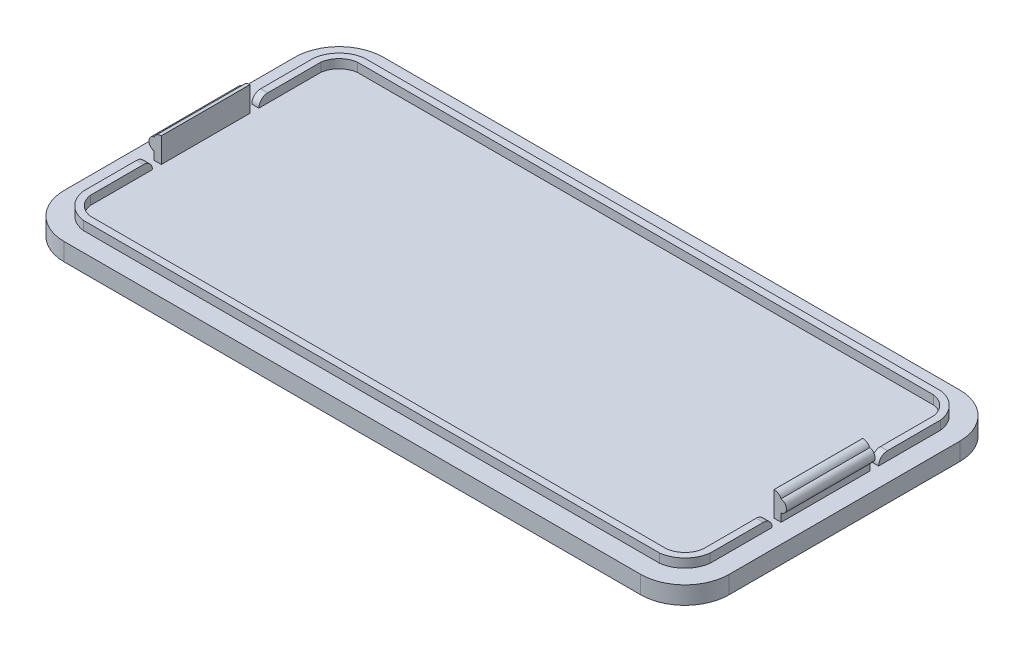
SolidWorks part; units mm, degrees
ref_plane "前视基准面" through (0, 0, 0) normal (0, 0, 1) x (1, 0, 0)
ref_plane "上视基准面" through (0, 0, 0) normal (0, 1, 0) x (1, 0, 0)
ref_plane "右视基准面" through (0, 0, 0) normal (1, 0, 0) x (0, 0, -1)
sketch "zero" plane through (0, 0, 0) normal (0, 1, 0) x (1, 0, 0)
  line L1 (-29.5, 15) -> (29.5, 15)
  line L2 (-32.5, 12) -> (-32.5, -12)
  line L3 (-29.5, -15) -> (29.5, -15)
  line L4 (32.5, 12) -> (32.5, -12)
  line L5 (-32.5, 15) -> (32.5, -15) construction
  line L6 (-32.5, -15) -> (32.5, 15) construction
  line L7 (-25.7, -15) -> (-14.5, -15)
  line L8 (-25.7, -15) -> (-25.7, -9.6569)
  line L9 (-25.7, -9.6569) -> (-14.5, -9.6569)
  line L10 (-14.5, -15) -> (-14.5, -9.6569)
  line L11 (5.2, -15) -> (12.7, -15)
  line L12 (5.2, -15) -> (5.2, -11)
  line L13 (5.2, -11) -> (12.7, -11)
  line L14 (12.7, -15) -> (12.7, -11)
  line L15 (17.8, -15) -> (25.3, -15)
  line L16 (17.8, -15) -> (17.8, -11)
  line L17 (17.8, -11) -> (25.3, -11)
  line L18 (25.3, -15) -> (25.3, -11)
  line L19 (-32.5, 7.7) -> (-19.5, 7.7)
  line L20 (-32.5, 7.7) -> (-32.5, -4.3)
  line L21 (-32.5, -4.3) -> (-19.5, -4.3)
  line L22 (-19.5, 7.7) -> (-19.5, -4.3)
  line L23 (-25.5, 14) -> (25.5, 14)
  line L24 (-25.5, 14) -> (-25.5, 8.8)
  line L25 (-25.5, 8.8) -> (25.5, 8.8)
  line L26 (25.5, 14) -> (25.5, 8.8)
  line L27 (-19.5, 7.2329) -> (-35.5, 7.2329)
  line L28 (-19.5, 7.2329) -> (-19.5, -3.7671)
  line L29 (-19.5, -3.7671) -> (-35.5, -3.7671)
  line L30 (-35.5, 7.2329) -> (-35.5, -3.7671)
  arc A0 (29.5, -15) -> (32.5, -12) centre (29.5, -12) ccw
  arc A1 (29.5, 15) -> (32.5, 12) centre (29.5, 12) cw
  arc A2 (-32.5, -12) -> (-29.5, -15) centre (-29.5, -12) ccw
  arc A3 (-29.5, 15) -> (-32.5, 12) centre (-29.5, 12) ccw
  circle A4 centre (-29, 11.4) radius 3
  circle A5 centre (-29, -11.5) radius 3
  circle A6 centre (29, 11.4) radius 3
  circle A7 centre (29, -11.5) radius 3
  circle A8 centre (-29, 11.4) radius 1.375
  circle A9 centre (-29, -11.5) radius 1.375
  circle A10 centre (29, -11.5) radius 1.375
  circle A11 centre (29, 11.4) radius 1.375
  point P0 (0, 0)
  dimension "D3" = 3
  dimension "D4" = 6
  dimension "D9" = 2.75
  dimension "D1" = 65
  dimension "D2" = 30
  dimension "D5" = 3.6
  dimension "D6" = 3.5
  dimension "D7" = 3.5
  dimension "D8" = 3.5
  dimension "D10" = 12
  dimension "D11" = 7.3
  dimension "D12" = 13
  dimension "D13" = 11.2
  dimension "D14" = 6.8
  dimension "D15" = 19.7
  dimension "D16" = 7.5
  dimension "D17" = 7.5
  dimension "D18" = 5.1
  dimension "D19" = 4
  dimension "D20" = 5.2
  dimension "D21" = 7
  dimension "D22" = 7
  dimension "D23" = 1
  dimension "D24" = 11
  dimension "D25" = 16
sketch "sugar" plane through (0, 0, 0) normal (0, 1, 0) x (1, 0, 0)
  line L1 (-29.5, 15) -> (29.5, 15)
  line L2 (-32.5, 12) -> (-32.5, -12)
  line L3 (-29.5, -15) -> (29.5, -15)
  line L4 (32.5, 12) -> (32.5, -12)
  line L5 (-32.5, 15) -> (32.5, -15) construction
  line L6 (-32.5, -15) -> (32.5, 15) construction
  line L7 (23.5, -11.5) -> (19.5, -11.5)
  line L8 (23.5, -11.5) -> (23.5, -13.9082)
  line L9 (23.5, -13.9082) -> (19.5, -13.9082)
  line L10 (19.5, -11.5) -> (19.5, -13.9082)
  line L11 (16, -11.0071) -> (8.5, -11.0071)
  line L12 (16, -11.0071) -> (16, -15)
  line L13 (16, -15) -> (8.5, -15)
  line L14 (8.5, -11.0071) -> (8.5, -15)
  line L15 (20.5, -13.9082) -> (22.5, -13.9082)
  line L16 (20.5, -13.9082) -> (20.5, -14.8173)
  line L17 (20.5, -14.8173) -> (22.5, -14.8173)
  line L18 (22.5, -13.9082) -> (22.5, -14.8173)
  arc A0 (29.5, 15) -> (32.5, 12) centre (29.5, 12) cw
  arc A1 (29.5, -15) -> (32.5, -12) centre (29.5, -12) ccw
  arc A2 (-32.5, -12) -> (-29.5, -15) centre (-29.5, -12) ccw
  arc A3 (-29.5, 15) -> (-32.5, 12) centre (-29.5, 12) ccw
  circle A4 centre (-29, 11.4) radius 3
  circle A5 centre (-29, 11.4) radius 1.375
  circle A6 centre (-29, -11.5) radius 3
  circle A7 centre (-29, -11.5) radius 1.375
  circle A8 centre (29, 11.4) radius 3
  circle A9 centre (29, 11.4) radius 1.375
  circle A10 centre (29, -11.5) radius 3
  circle A11 centre (29, -11.5) radius 1.375
  dimension "D3" = 3
  dimension "D1" = 65
  dimension "D2" = 30
  dimension "D4" = 9
  dimension "D5" = 4
  dimension "D6" = 3.5
  dimension "D7" = 7.5
  dimension "D8" = 2
  dimension "D9" = 1
sketch "case" plane through (0, 0, 0) normal (0, 1, 0) x (1, 0, 0)
  line L1 (-34.0422, 18) -> (30.9578, 18)
  line L2 (-39.0422, 13) -> (-39.0422, -13)
  line L3 (-34.0422, -18) -> (30.9578, -18)
  line L4 (35.9578, 13) -> (35.9578, -13)
  line L5 (-39.0422, 18) -> (35.9578, -18) construction
  line L6 (-39.0422, -18) -> (35.9578, 18) construction
  arc A0 (-39.0422, -13) -> (-34.0422, -18) centre (-34.0422, -13) ccw
  arc A1 (30.9578, -18) -> (35.9578, -13) centre (30.9578, -13) ccw
  arc A2 (30.9578, 18) -> (35.9578, 13) centre (30.9578, 13) cw
  arc A3 (-34.0422, 18) -> (-39.0422, 13) centre (-34.0422, 13) ccw
  point P0 (-1.5422, 0)
  point P3 (-1.5422, 0)
  dimension "D3" = 5
  dimension "D1" = 75
  dimension "D2" = 36
extrude "凸台-拉伸2" add sketch "case" along normal blind 2
sketch "草图2" plane through (0, 0, 0) normal (0, 1, 0) x (1, 0, 0)
  line L4 (-34.0422, -15.05) -> (30.9578, -15.05)
  line L5 (33.0078, -13) -> (33.0078, 13)
  line L6 (30.9578, 15.05) -> (-34.0422, 15.05)
  line L7 (-36.0922, 13) -> (-36.0922, -13)
  line L12 (33.8078, -13) -> (33.8078, 13)
  line L13 (30.9578, 15.85) -> (-34.0422, 15.85)
  line L14 (-36.8922, 13) -> (-36.8922, -13)
  line L15 (-34.0422, -15.85) -> (30.9578, -15.85)
  arc A4 (30.9578, -15.05) -> (33.0078, -13) centre (30.6303, -12.6725) ccw
  arc A5 (33.0078, 13) -> (30.9578, 15.05) centre (30.6303, 12.6725) ccw
  arc A6 (-34.0422, 15.05) -> (-36.0922, 13) centre (-33.7147, 12.6725) ccw
  arc A7 (-36.0922, -13) -> (-34.0422, -15.05) centre (-33.7147, -12.6725) ccw
  arc A12 (30.9578, -15.85) -> (33.8078, -13) centre (30.535, -12.5772) ccw
  arc A13 (33.8078, 13) -> (30.9578, 15.85) centre (30.535, 12.5772) ccw
  arc A14 (-34.0422, 15.85) -> (-36.8922, 13) centre (-33.6194, 12.5772) ccw
  arc A15 (-36.8922, -13) -> (-34.0422, -15.85) centre (-33.6194, -12.5772) ccw
ref_plane "基准面1" through (0, 2, 0) normal (0, 1, 0) x (1, 0, 0)
sketch "草图3" plane through (0, 2, 0) normal (0, 1, 0) x (1, 0, 0)
  line L4 (-34.0422, -15.05) -> (30.9578, -15.05)
  line L5 (33.0078, -13) -> (33.0078, 13)
  line L6 (30.9578, 15.05) -> (-34.0422, 15.05)
  line L7 (-36.0922, 13) -> (-36.0922, -13)
  line L8 (-34.0422, -15.05) -> (30.9578, -15.05)
  line L9 (33.0078, -13) -> (33.0078, 13)
  line L10 (30.9578, 15.05) -> (-34.0422, 15.05)
  line L11 (-36.0922, 13) -> (-36.0922, -13)
  line L12 (-36.8922, 13) -> (-36.8922, -13)
  line L13 (-34.0422, -15.85) -> (30.9578, -15.85)
  line L14 (33.8078, -13) -> (33.8078, 13)
  line L15 (30.9578, 15.85) -> (-34.0422, 15.85)
  line L16 (-36.8922, 13) -> (-36.8922, -13)
  line L17 (-34.0422, -15.85) -> (30.9578, -15.85)
  line L18 (33.8078, -13) -> (33.8078, 13)
  line L19 (30.9578, 15.85) -> (-34.0422, 15.85)
  arc A4 (30.9578, -15.05) -> (33.0078, -13) centre (30.6303, -12.6725) ccw
  arc A5 (33.0078, 13) -> (30.9578, 15.05) centre (30.6303, 12.6725) ccw
  arc A6 (-34.0422, 15.05) -> (-36.0922, 13) centre (-33.7147, 12.6725) ccw
  arc A7 (-36.0922, -13) -> (-34.0422, -15.05) centre (-33.7147, -12.6725) ccw
  arc A8 (30.9578, -15.05) -> (33.0078, -13) centre (30.6303, -12.6725) ccw
  arc A9 (33.0078, 13) -> (30.9578, 15.05) centre (30.6303, 12.6725) ccw
  arc A10 (-34.0422, 15.05) -> (-36.0922, 13) centre (-33.7147, 12.6725) ccw
  arc A11 (-36.0922, -13) -> (-34.0422, -15.05) centre (-33.7147, -12.6725) ccw
  arc A12 (-36.8922, -13) -> (-34.0422, -15.85) centre (-33.6194, -12.5772) ccw
  arc A13 (30.9578, -15.85) -> (33.8078, -13) centre (30.535, -12.5772) ccw
  arc A14 (33.8078, 13) -> (30.9578, 15.85) centre (30.535, 12.5772) ccw
  arc A15 (-34.0422, 15.85) -> (-36.8922, 13) centre (-33.6194, 12.5772) ccw
  arc A16 (-36.8922, -13) -> (-34.0422, -15.85) centre (-33.6194, -12.5772) ccw
  arc A17 (30.9578, -15.85) -> (33.8078, -13) centre (30.535, -12.5772) ccw
  arc A18 (33.8078, 13) -> (30.9578, 15.85) centre (30.535, 12.5772) ccw
  arc A19 (-34.0422, 15.85) -> (-36.8922, 13) centre (-33.6194, 12.5772) ccw
  dimension "D1" = 0
  dimension "D2" = 0
extrude "凸台-拉伸4" add sketch "草图3" along normal blind 1
ref_plane "基准面3" through (33.8078, 0, 0) normal (1, 0, 0) x (0, 0, -1)
sketch "草图7" plane through (0, 2, 0) normal (0, 1, 0) x (1, 0, 0)
  line L0 (-36.8922, 13) -> (-36.8922, -13) construction
  line L1 (-36.8922, 5) -> (-36.0922, 5)
  line L2 (-36.8922, 5) -> (-36.8922, -5)
  line L3 (-36.8922, -5) -> (-36.0922, -5)
  line L4 (-36.0922, 5) -> (-36.0922, -5)
  line L5 (-36.0922, 13) -> (-36.0922, -13) construction
  point P10 (-36.0922, 0)
  dimension "D1" = 5
  dimension "D2" = 10
extrude "凸台-拉伸8" add sketch "草图7" along normal blind 2.8
ref_plane "基准面5" through (0, 0, 5) normal (0, 0, 1) x (1, 0, 0)
sketch "草图8" plane through (0, 0, 5) normal (0, 0, 1) x (1, 0, 0)
  line L0 (-34.0422, 2) -> (-39.0422, 2) construction
  line L1 (-36.8922, 4.8) -> (-36.8922, 3) construction
  circle A0 centre (-36.7922, 3.6) radius 0.7
  dimension "D1" = 1.4
  dimension "D2" = 1.6
  dimension "D3" = 0.1
extrude "凸台-拉伸9" add sketch "草图8" against normal blind 10
fillet "圆角1" radius 0.85 1 edges at (-36.8922, 4.8, 0)
ref_plane "基准面7" through (-36.8922, 0, 0) normal (-1, 0, 0) x (0, 0, 1)
sketch "草图11" plane through (-36.8922, 0, 0) normal (-1, 0, 0) x (0, 0, 1)
  line L0 (-13, 2) -> (13, 2) construction
  line L1 (5, 3) -> (6, 3)
  line L2 (5, 3) -> (5, 2)
  line L3 (5, 2) -> (6, 2)
  line L4 (6, 3) -> (6, 2)
  line L6 (-5, 3) -> (-6, 3)
  line L7 (-5, 3) -> (-5, 2)
  line L8 (-5, 2) -> (-6, 2)
  line L9 (-6, 3) -> (-6, 2)
  dimension "D1" = 1
  dimension "D2" = 1
extrude "切除-拉伸1" cut sketch "草图11" against normal blind 1.2
fillet "圆角2" radius 1 2 edges at (-36.4922, 3, 6) (-36.4922, 3, -6)
ref_plane "基准面8" through (0, 0, 0) normal (0, -1, 0) x (-1, 0, 0)
sketch "草图12" plane through (0, 0, 0) normal (0, -1, 0) x (-1, 0, 0)
  line L76 (34.0422, -18) -> (-30.9578, -18) construction
  line L78 (39.0422, 13) -> (39.0422, -13) construction
  line B0 (-8.1993, 5.026) -> (-9.0198, 5.499)
  line B1 (-9.0198, 5.499) -> (-13.2767, 7.9551)
  line B2 (-13.2767, 7.9551) -> (-14.0973, 8.4339)
  line B3 (-15.8183, 8.4339) -> (-16.6389, 7.9551)
  line B4 (-16.6389, 7.9551) -> (-20.8958, 5.499)
  line B5 (-20.8958, 5.499) -> (-21.7165, 5.026)
  line B6 (-22.577, 3.5387) -> (-22.577, -3.2769)
  line B7 (-21.7165, -4.7643) -> (-20.8958, -5.2373)
  line B8 (-20.8958, -5.2373) -> (-16.6389, -7.6934)
  line B9 (-16.6389, -7.6934) -> (-15.8183, -8.172)
  line B10 (-14.0973, -8.172) -> (-13.2767, -7.6934)
  line B11 (-13.2767, -7.6934) -> (-9.0198, -5.2373)
  line B12 (-9.0198, -5.2373) -> (-8.1993, -4.7643)
  line B13 (-7.3388, -3.2769) -> (-7.3388, 3.5387)
  line B14 (-20.6223, 4.3479) -> (-15.3568, 7.391)
  line B15 (-14.5532, 7.391) -> (-9.3162, 4.3422)
  line B16 (-9.3105, 3.6413) -> (-14.3993, 0.5982)
  line B17 (-12.8208, -4.5591) -> (-13.4135, -4.8896)
  line B18 (-13.4705, -4.9865) -> (-13.4705, -6.6961)
  line B19 (-13.5274, -6.793) -> (-14.633, -7.4198)
  line B20 (-14.7983, -7.3229) -> (-14.7983, -2.046)
  line B21 (-14.7413, -1.9491) -> (-12.8607, -0.8835)
  line B22 (-8.9173, -4.2058) -> (-10.0114, -4.8269)
  line B23 (-10.1767, -4.7301) -> (-10.1767, -2.2169)
  line B24 (-10.1197, -2.1201) -> (-9.0256, -1.5046)
  line B25 (-8.8603, -1.6015) -> (-8.8603, -4.1089)
  line B26 (-12.8893, -3.5447) -> (-13.4135, -3.8069)
  line B27 (-13.4705, -3.6872) -> (-13.4705, -2.3423)
  line B28 (-13.4135, -2.2455) -> (-12.9234, -1.9719)
  line B29 (-3.344, 3.06) -> (-5.2189, 3.06)
  line B30 (-5.2189, 3.06) -> (-5.2189, -3.5048)
  line B31 (-5.2189, -3.5048) -> (-4.3868, -3.5048)
  line B32 (-4.3868, -3.5048) -> (-4.3868, -0.9005)
  line B33 (-4.3868, -0.9005) -> (-3.2984, -0.9005)
  line B34 (-3.4066, -0.2281) -> (-4.3868, -0.2281)
  line B35 (-4.3868, -0.2281) -> (-4.3868, 2.3876)
  line B36 (-4.3868, 2.3876) -> (-3.4408, 2.3876)
  line B37 (0.1948, 1.3618) -> (0.1948, -3.5048)
  line B38 (0.1948, -3.5048) -> (1.0098, -3.5048)
  line B39 (1.0098, -3.5048) -> (1.0098, 1.3618)
  line B40 (1.0098, 1.3618) -> (0.1948, 1.3618)
  line B41 (5.7169, 0.2847) -> (4.8849, 0.6153)
  line B42 (6.0417, 1.4017) -> (6.8396, 2.4047)
  line B43 (3.6084, -0.5586) -> (4.4575, -0.9177)
  line B44 (2.9074, -1.5673) -> (2.0014, -2.6729)
  line B45 (10.8229, 1.5898) -> (10.8229, -1.7497)
  line B46 (9.3811, -1.3621) -> (9.3811, 1.5898)
  line B47 (9.3811, 1.5898) -> (7.7912, 1.5898)
  line B48 (7.7912, 1.5898) -> (7.7912, -1.5616)
  line B49 (10.9711, -2.8039) -> (11.0052, -2.8039)
  line B50 (11.0052, -2.8039) -> (11.1193, -3.5048)
  line B51 (11.1193, -3.5048) -> (12.4185, -3.5048)
  line B52 (12.4185, -3.5048) -> (12.4185, 1.5898)
  line B53 (12.4185, 1.5898) -> (10.8229, 1.5898)
  line B54 (16.2708, -2.5019) -> (15.4673, -2.5019)
  line B55 (17.365, 0.4386) -> (18.1513, 0.4386)
  line B56 (18.1513, 0.4386) -> (18.1513, 1.5898)
  line B57 (18.1513, 1.5898) -> (16.2822, 1.5898)
  line B58 (14.0312, -1.4533) -> (14.0312, -1.4875)
  line B59 (13.9344, -3.3168) -> (13.9344, -3.3624)
  line B60 (15.4844, -3.7214) -> (15.9688, -3.7214)
  line B61 (18.6072, 1.0484) -> (19.1657, -0.0002)
  line B62 (21.411, -2.992) -> (21.4508, -2.992)
  line B63 (21.4508, -2.992) -> (21.5648, -3.5048)
  line B64 (21.5648, -3.5048) -> (22.8641, -3.5048)
  line B65 (22.8641, -3.5048) -> (22.8641, -0.6099)
  line B66 (21.2685, -1.1741) -> (21.2685, -1.989)
  line B67 (25.3545, 0.7065) -> (25.3203, 0.7065)
  line B68 (25.3203, 0.7065) -> (25.212, 1.5898)
  line B69 (25.212, 1.5898) -> (23.9127, 1.5898)
  line B70 (23.9127, 1.5898) -> (23.9127, -3.5048)
  line B71 (23.9127, -3.5048) -> (25.4969, -3.5048)
  line B72 (25.4969, -3.5048) -> (25.4969, -0.5928)
  line B73 (27.1552, 0.2392) -> (27.423, 1.6125)
  line B74 (-13.4135, -3.8069) -> (-13.4135, -4.8896)
  line B75 (-13.4705, -3.6872) -> (-13.4705, -4.9865)
  spline B76 degree 3 poles (-14.0973, 8.4339) (-14.3652, 8.582) (-14.6615, 8.6618) (-14.9578, 8.6618) knots 3 3 3 3 4 4 4 4
  spline B77 degree 3 poles (-14.9578, 8.6618) (-15.2541, 8.6618) (-15.5505, 8.582) (-15.8183, 8.4339) knots 4 4 4 4 5 5 5 5
  spline B78 degree 3 poles (-21.7165, 5.026) (-22.2464, 4.7183) (-22.577, 4.1485) (-22.577, 3.5387) knots 8 8 8 8 9 9 9 9
  spline B79 degree 3 poles (-22.577, -3.2769) (-22.577, -3.8923) (-22.2464, -4.4565) (-21.7165, -4.7643) knots 10 10 10 10 11 11 11 11
  spline B80 degree 3 poles (-15.8183, -8.172) (-15.5505, -8.3259) (-15.2541, -8.4) (-14.9578, -8.4) knots 14 14 14 14 15 15 15 15
  spline B81 degree 3 poles (-14.9578, -8.4) (-14.6615, -8.4) (-14.3652, -8.3259) (-14.0973, -8.172) knots 15 15 15 15 16 16 16 16
  spline B82 degree 3 poles (-8.1993, -4.7643) (-7.6636, -4.4565) (-7.3388, -3.8923) (-7.3388, -3.2769) knots 19 19 19 19 20 20 20 20
  spline B83 degree 3 poles (-7.3388, 3.5387) (-7.3388, 4.1485) (-7.6636, 4.7183) (-8.1993, 5.026) knots 21 21 21 21 22 22 22 22
  spline B84 degree 2 poles (-15.5106, 0.5982) (-20.6622, 3.5729) (-20.6736, 3.5786) knots 0 0 0 1 1 1
  spline B85 degree 3 poles (-20.6736, 3.5786) (-20.9414, 3.7723) (-20.9129, 4.1826) (-20.6223, 4.3479) knots 1 1 1 1 2 2 2 2
  spline B86 degree 3 poles (-15.3568, 7.391) (-15.1117, 7.5335) (-14.8039, 7.5335) (-14.5532, 7.391) knots 3 3 3 3 4 4 4 4
  spline B87 degree 3 poles (-9.3162, 4.3422) (-9.0484, 4.1883) (-9.0427, 3.8008) (-9.3105, 3.6413) knots 5 5 5 5 6 6 6 6
  spline B88 degree 3 poles (-14.3993, 0.5982) (-14.7413, 0.3987) (-15.1687, 0.3987) (-15.5106, 0.5982) knots 7 7 7 7 8 8 8 8
  spline B89 degree 3 poles (-13.4705, -6.6961) (-13.4705, -6.736) (-13.4876, -6.7702) (-13.5274, -6.793) knots 3 3 3 3 4 4 4 4
  spline B90 degree 3 poles (-14.633, -7.4198) (-14.7071, -7.4597) (-14.7983, -7.4084) (-14.7983, -7.3229) knots 5 5 5 5 6 6 6 6
  spline B91 degree 3 poles (-14.7983, -2.046) (-14.7983, -2.0061) (-14.7812, -1.9662) (-14.7413, -1.9491) knots 7 7 7 7 8 8 8 8
  spline B92 degree 3 poles (-12.8607, -0.8835) (-11.6412, -0.1939) (-10.6326, -0.0572) (-10.6326, -1.4249) knots 9 9 9 9 10 10 10 10
  spline B93 degree 3 poles (-10.6326, -1.4249) (-10.6326, -2.7412) (-11.6526, -3.898) (-12.8208, -4.5591) knots 10 10 10 10 11 11 11 11
  spline B94 degree 3 poles (-8.8603, -4.1089) (-8.8603, -4.1488) (-8.8831, -4.1887) (-8.9173, -4.2058) knots 0 0 0 0 1 1 1 1
  spline B95 degree 3 poles (-10.0114, -4.8269) (-10.0855, -4.8668) (-10.1767, -4.8155) (-10.1767, -4.7301) knots 2 2 2 2 3 3 3 3
  spline B96 degree 3 poles (-10.1767, -2.2169) (-10.1767, -2.1771) (-10.1539, -2.1429) (-10.1197, -2.1201) knots 4 4 4 4 5 5 5 5
  spline B97 degree 3 poles (-9.0256, -1.5046) (-8.9515, -1.4647) (-8.8603, -1.516) (-8.8603, -1.6015) knots 6 6 6 6 7 7 7 7
  spline B98 degree 3 poles (-9.5156, 0.1651) (-9.0768, 0.4158) (-8.7634, 0.3076) (-8.7634, -0.0914) (-8.7634, -0.4846) (-9.0768, -0.9461) (-9.5156, -1.1912) knots 2 2 2 2 3 3 3 4 4 4 4
  spline B99 degree 3 poles (-9.5156, -1.1912) (-9.9601, -1.4476) (-10.2735, -1.3394) (-10.2735, -0.9461) (-10.2735, -0.5415) (-9.9601, -0.0856) (-9.5156, 0.1651) knots 0 0 0 0 1 1 1 2 2 2 2
  spline B100 degree 3 poles (-11.9319, -2.16) (-11.9319, -2.7013) (-12.2395, -3.18) (-12.8893, -3.5447) knots 0 0 0 0 1 1 1 1
  spline B101 degree 3 poles (-13.4705, -2.3423) (-13.4705, -2.3024) (-13.4477, -2.2625) (-13.4135, -2.2455) knots 4 4 4 4 5 5 5 5
  spline B102 degree 3 poles (-12.9234, -1.9719) (-12.2852, -1.6072) (-11.9319, -1.6015) (-11.9319, -2.16) knots 6 6 6 6 7 7 7 7
  spline B103 degree 3 poles (-3.2984, -0.9005) (-1.868, -0.9005) (-0.8822, -0.2509) (-0.8822, 1.1339) knots 5 5 5 5 6 6 6 6
  spline B104 degree 3 poles (-0.8822, 1.1339) (-0.8822, 2.5699) (-1.868, 3.06) (-3.344, 3.06) knots 6 6 6 6 7 7 7 7
  spline B105 degree 3 poles (-3.4408, 2.3876) (-2.2897, 2.3876) (-1.7084, 2.0855) (-1.7084, 1.1339) knots 3 3 3 3 4 4 4 4
  spline B106 degree 3 poles (-1.7084, 1.1339) (-1.7084, 0.1936) (-2.2498, -0.2281) (-3.4066, -0.2281) knots 4 4 4 4 5 5 5 5
  spline B107 degree 3 poles (0.6052, 2.3648) (0.93, 2.3648) (1.1694, 2.587) (1.1694, 2.889) (1.1694, 3.2253) (0.93, 3.419) (0.6052, 3.419) knots 2 2 2 2 3 3 3 4 4 4 4
  spline B108 degree 3 poles (0.6052, 3.419) (0.2804, 3.419) (0.041, 3.2253) (0.041, 2.889) (0.041, 2.587) (0.2804, 2.3648) (0.6052, 2.3648) knots 0 0 0 0 1 1 1 2 2 2 2
  spline B109 degree 3 poles (4.8849, 0.6153) (4.2979, 0.8489) (3.8762, 0.9914) (3.8762, 1.3618) knots 1 1 1 1 2 2 2 2
  spline B110 degree 3 poles (3.8762, 1.3618) (3.8762, 1.7151) (4.1783, 1.9146) (4.674, 1.9146) knots 2 2 2 2 3 3 3 3
  spline B111 degree 3 poles (4.674, 1.9146) (5.1926, 1.9146) (5.6029, 1.7379) (6.0417, 1.4017) knots 3 3 3 3 4 4 4 4
  spline B112 degree 3 poles (6.8396, 2.4047) (6.2583, 2.9916) (5.4433, 3.2879) (4.674, 3.2879) knots 5 5 5 5 6 6 6 6
  spline B113 degree 3 poles (4.674, 3.2879) (3.2551, 3.2879) (2.2521, 2.3876) (2.2521, 1.2706) knots 6 6 6 6 7 7 7 7
  spline B114 degree 3 poles (2.2521, 1.2706) (2.2521, 0.3019) (2.9074, -0.2794) (3.6084, -0.5586) knots 7 7 7 7 8 8 8 8
  spline B115 degree 3 poles (4.4575, -0.9177) (5.0274, -1.157) (5.3978, -1.2824) (5.3978, -1.6699) knots 9 9 9 9 10 10 10 10
  spline B116 degree 3 poles (5.3978, -1.6699) (5.3978, -2.0289) (5.1185, -2.2511) (4.5259, -2.2511) knots 10 10 10 10 11 11 11 11
  spline B117 degree 3 poles (4.5259, -2.2511) (4.0016, -2.2511) (3.3804, -1.9719) (2.9074, -1.5673) knots 11 11 11 11 12 12 12 12
  spline B118 degree 3 poles (2.0014, -2.6729) (2.6909, -3.3054) (3.6254, -3.6302) (4.4916, -3.6302) knots 13 13 13 13 14 14 14 14
  spline B119 degree 3 poles (4.4916, -3.6302) (6.1044, -3.6302) (7.0389, -2.6557) (7.0389, -1.5445) knots 14 14 14 14 15 15 15 15
  spline B120 degree 3 poles (7.0389, -1.5445) (7.0389, -0.6042) (6.5432, -0.0458) (5.7169, 0.2847) knots 15 15 15 15 16 16 16 16
  spline B121 degree 3 poles (10.8229, -1.7497) (10.5551, -2.1258) (10.3328, -2.2682) (9.9738, -2.2682) knots 1 1 1 1 2 2 2 2
  spline B122 degree 3 poles (9.9738, -2.2682) (9.5692, -2.2682) (9.3811, -2.0688) (9.3811, -1.3621) knots 2 2 2 2 3 3 3 3
  spline B123 degree 3 poles (7.7912, -1.5616) (7.7912, -2.8324) (8.2642, -3.6302) (9.3754, -3.6302) knots 6 6 6 6 7 7 7 7
  spline B124 degree 3 poles (9.3754, -3.6302) (10.0706, -3.6302) (10.5494, -3.3054) (10.9711, -2.8039) knots 7 7 7 7 8 8 8 8
  spline B125 degree 3 poles (15.4673, -2.5019) (14.9202, -2.5019) (14.7151, -2.3936) (14.7151, -2.16) knots 1 1 1 1 2 2 2 2
  spline B126 degree 3 poles (14.7151, -2.16) (14.7151, -1.989) (14.7549, -1.9092) (14.8746, -1.8009) knots 2 2 2 2 3 3 3 3
  spline B127 degree 3 poles (14.8746, -1.8009) (15.0969, -1.8636) (15.302, -1.8921) (15.473, -1.8921) knots 3 3 3 3 4 4 4 4
  spline B128 degree 3 poles (15.473, -1.8921) (16.6013, -1.8921) (17.5074, -1.3735) (17.5074, -0.1825) knots 4 4 4 4 5 5 5 5
  spline B129 degree 3 poles (17.5074, -0.1825) (17.5074, 0.0625) (17.4447, 0.2962) (17.365, 0.4386) knots 5 5 5 5 6 6 6 6
  spline B130 degree 3 poles (16.2822, 1.5898) (16.0485, 1.6752) (15.7693, 1.7151) (15.473, 1.7151) knots 9 9 9 9 10 10 10 10
  spline B131 degree 3 poles (15.473, 1.7151) (14.3732, 1.7151) (13.3417, 1.1111) (13.3417, -0.1369) knots 10 10 10 10 11 11 11 11
  spline B132 degree 3 poles (13.3417, -0.1369) (13.3417, -0.7296) (13.6722, -1.2026) (14.0312, -1.4533) knots 11 11 11 11 12 12 12 12
  spline B133 degree 3 poles (14.0312, -1.4875) (13.7007, -1.7212) (13.467, -2.0802) (13.467, -2.4392) knots 13 13 13 13 14 14 14 14
  spline B134 degree 3 poles (13.467, -2.4392) (13.467, -2.8666) (13.6665, -3.1344) (13.9344, -3.3168) knots 14 14 14 14 15 15 15 15
  spline B135 degree 3 poles (13.9344, -3.3624) (13.4613, -3.6017) (13.2106, -3.9436) (13.2106, -4.3653) knots 16 16 16 16 17 17 17 17
  spline B136 degree 3 poles (13.2106, -4.3653) (13.2106, -5.2771) (14.1737, -5.6475) (15.3476, -5.6475) knots 17 17 17 17 18 18 18 18
  spline B137 degree 3 poles (15.3476, -5.6475) (17.1199, -5.6475) (18.2312, -4.8839) (18.2312, -3.8069) knots 18 18 18 18 19 19 19 19
  spline B138 degree 3 poles (18.2312, -3.8069) (18.2312, -2.8837) (17.5245, -2.5019) (16.2708, -2.5019) knots 19 19 19 19 20 20 20 20
  spline B139 degree 3 poles (15.473, -0.9347) (15.1083, -0.9347) (14.8291, -0.6669) (14.8291, -0.1369) (14.8291, 0.3816) (15.1083, 0.6495) (15.473, 0.6495) knots 2 2 2 2 3 3 3 4 4 4 4
  spline B140 degree 3 poles (15.473, 0.6495) (15.8491, 0.6495) (16.1169, 0.3816) (16.1169, -0.1369) (16.1169, -0.6669) (15.8491, -0.9347) (15.473, -0.9347) knots 0 0 0 0 1 1 1 2 2 2 2
  spline B141 degree 3 poles (15.5983, -4.6503) (14.943, -4.6503) (14.5156, -4.4736) (14.5156, -4.1146) knots 0 0 0 0 1 1 1 1
  spline B142 degree 3 poles (14.5156, -4.1146) (14.5156, -3.9436) (14.5953, -3.8012) (14.7549, -3.6587) knots 1 1 1 1 2 2 2 2
  spline B143 degree 3 poles (14.7549, -3.6587) (14.9202, -3.7043) (15.114, -3.7214) (15.4844, -3.7214) knots 2 2 2 2 3 3 3 3
  spline B144 degree 3 poles (15.9688, -3.7214) (16.4417, -3.7214) (16.7096, -3.7841) (16.7096, -4.0861) knots 4 4 4 4 5 5 5 5
  spline B145 degree 3 poles (16.7096, -4.0861) (16.7096, -4.4109) (16.2537, -4.6503) (15.5983, -4.6503) knots 5 5 5 5 6 6 6 6
  spline B146 degree 3 poles (20.8013, 1.7151) (20.0091, 1.7151) (19.2797, 1.4473) (18.6072, 1.0484) knots 0 0 0 0 1 1 1 1
  spline B147 degree 3 poles (19.1657, -0.0002) (19.6729, 0.2847) (20.0946, 0.4443) (20.4992, 0.4443) knots 2 2 2 2 3 3 3 3
  spline B148 degree 3 poles (20.4992, 0.4443) (21.0177, 0.4443) (21.2344, 0.205) (21.2685, -0.2053) knots 3 3 3 3 4 4 4 4
  spline B149 degree 3 poles (21.2685, -0.2053) (19.2797, -0.4219) (18.4362, -1.0031) (18.4362, -2.0802) knots 4 4 4 4 5 5 5 5
  spline B150 degree 3 poles (18.4362, -2.0802) (18.4362, -2.9293) (19.0118, -3.6302) (19.9522, -3.6302) knots 5 5 5 5 6 6 6 6
  spline B151 degree 3 poles (19.9522, -3.6302) (20.5163, -3.6302) (20.9893, -3.3681) (21.411, -2.992) knots 6 6 6 6 7 7 7 7
  spline B152 degree 3 poles (22.8641, -0.6099) (22.8641, 0.9857) (22.1176, 1.7151) (20.8013, 1.7151) knots 11 11 11 11 12 12 12 12
  spline B153 degree 3 poles (21.2685, -1.989) (21.0349, -2.2398) (20.824, -2.3936) (20.4992, -2.3936) knots 0 0 0 0 1 1 1 1
  spline B154 degree 3 poles (20.4992, -2.3936) (20.1686, -2.3936) (19.9522, -2.2511) (19.9522, -1.9548) knots 1 1 1 1 2 2 2 2
  spline B155 degree 3 poles (19.9522, -1.9548) (19.9522, -1.5958) (20.277, -1.3109) (21.2685, -1.1741) knots 2 2 2 2 3 3 3 3
  spline B156 degree 3 poles (26.8076, 1.7151) (26.2947, 1.7151) (25.7305, 1.3846) (25.3545, 0.7065) knots 0 0 0 0 1 1 1 1
  spline B157 degree 3 poles (25.4969, -0.5928) (25.7648, 0.0796) (26.2207, 0.3189) (26.5967, 0.3189) knots 7 7 7 7 8 8 8 8
  spline B158 degree 3 poles (26.5967, 0.3189) (26.8247, 0.3189) (26.9729, 0.2847) (27.1552, 0.2392) knots 8 8 8 8 9 9 9 9
  spline B159 degree 3 poles (27.423, 1.6125) (27.2806, 1.6752) (27.1096, 1.7151) (26.8076, 1.7151) knots 10 10 10 10 11 11 11 11
  dimension "D1" = 9.6
  dimension "D2" = 54
sketch_block_instance "块1-1"
sketch_block "块1"
extrude "切除-拉伸2" cut sketch "草图12" against normal blind 0.5
sketch "草图13" plane through (0, 3, 0) normal (0, 1, 0) x (1, 0, 0)
  line L0 (33.0078, -13) -> (33.0078, 13) construction
  line L1 (33.0078, 5) -> (33.8078, 5)
  line L2 (33.0078, 5) -> (33.0078, -5)
  line L3 (33.0078, -5) -> (33.8078, -5)
  line L4 (33.8078, 5) -> (33.8078, -5)
  line L5 (33.8078, -13) -> (33.8078, 13) construction
  line L7 (35.9578, -13) -> (35.9578, 13) construction
  point P12 (35.9578, 0)
  point P13 (33.8078, 0)
  dimension "D1" = 10
extrude "凸台-拉伸10" add sketch "草图13" along normal blind 1.8
sketch "草图14" plane through (0, 0, 5) normal (0, 0, 1) x (1, 0, 0)
  line L0 (33.8078, 2) -> (30.9578, 2) construction
  line L1 (33.8078, 4.8) -> (33.8078, 3) construction
  circle A0 centre (33.7078, 3.6) radius 0.7
  dimension "D2" = 1.4
  dimension "D1" = 1.6
  dimension "D3" = 0.1
extrude "凸台-拉伸11" add sketch "草图14" against normal blind 10
fillet "圆角3" radius 0.85 1 edges at (33.8078, 4.8, 0)
sketch "草图15" plane through (0, 3, 0) normal (0, 1, 0) x (1, 0, 0)
  line L0 (33.8078, 5) -> (33.8078, 13) construction
  line L1 (33.0078, 5) -> (33.8078, 5)
  line L2 (33.0078, 5) -> (33.0078, 6)
  line L3 (33.0078, 6) -> (33.8078, 6)
  line L4 (33.8078, 5) -> (33.8078, 6)
  line L5 (33.8078, -13) -> (33.8078, -5) construction
  line L6 (33.0078, -5) -> (33.8078, -5)
  line L7 (33.0078, -5) -> (33.0078, -6)
  line L8 (33.0078, -6) -> (33.8078, -6)
  line L9 (33.8078, -5) -> (33.8078, -6)
  dimension "D1" = 1
  dimension "D2" = 1
extrude "切除-拉伸3" cut sketch "草图15" against normal blind 1
fillet "圆角4" radius 1 2 edges at (33.4078, 3, 6) (33.4078, 3, -6)
